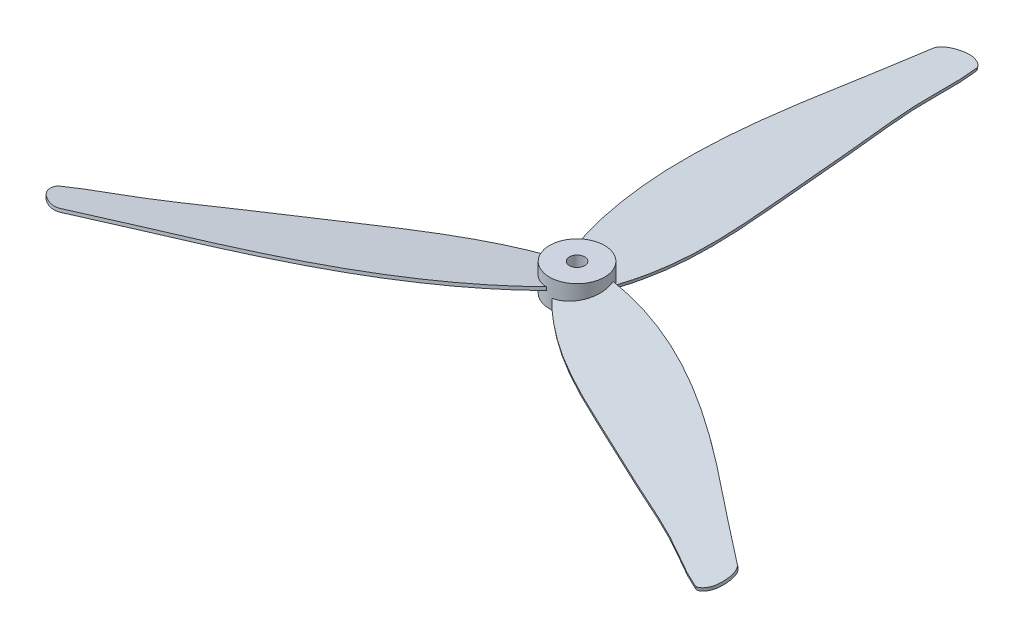
SolidWorks part; units mm, degrees
material "A-Glass Fiber"
ref_plane "Front Plane" through (0, 0, 0) normal (0, 0, 1) x (1, 0, 0)
ref_plane "Top Plane" through (0, 0, 0) normal (0, 1, 0) x (1, 0, 0)
ref_plane "Right Plane" through (0, 0, 0) normal (1, 0, 0) x (0, 0, -1)
sketch "Sketch1" plane through (0, 0, 0) normal (0, 1, 0) x (1, 0, 0)
  circle A0 centre (0, 0) radius 9
  circle A1 centre (0, 0) radius 2.5
  dimension "D1" = 18
  dimension "D2" = 5
extrude "Boss-Extrude1" add sketch "Sketch1" along normal blind 9
sketch "Sketch3" plane through (0, 0, 0) normal (0, 1, 0) x (1, 0, 0)
  line L0 (0, 0) -> (0, 32.3409) construction
  line L1 (0, 0) -> (86.3188, -49.8362) construction
  dimension "D1" = 120
ref_plane "Plane1" through (0, 0, 0) normal (-0.0782, 0.9877, 0.1355) x (0.866, 0, 0.5)
sketch "Sketch2" plane through (0, 0, 0) normal (0.0782, -0.9877, -0.1355) x (0.5031, -0.0782, 0.8607)
  line L0 (-0.0729, 0) -> (109.2834, -64.577) construction
  arc A3 (7.0572, 3.5223) -> (-0.8103, -7.8456) centre (0, 0) cw
  spline S0 degree 3 poles (-0.8103, -7.8456) (14.8456, -26.5282) (50.11, -46.9687) (87.5823, -60.2779) (104.3944, -67.4966) (108.6947, -65.6224) (111.8395, -62.2937) (111.6744, -59.1449) (110.3348, -58.1895) (105.388, -54.6473) (93.4703, -48.5314) (77.381, -36.6533) (48.7521, -17.4899) (26.9641, -1.2792) (7.0572, 3.5223) knots 0 0 0 0 0.282933 0.466483 0.471857 0.495006 0.514383 0.523355 0.526651 0.533187 0.595375 0.682473 0.767936 1 1 1 1
  dimension "D1" = 127
extrude "Boss-Extrude2" add sketch "Sketch2" along normal blind 1 from offset 4.5 offset against normal yes
pattern_circular "CirPattern1" count 3 over 360 about axis through (0, 9, 0) along (0, 1, 0) of "Boss-Extrude2"
